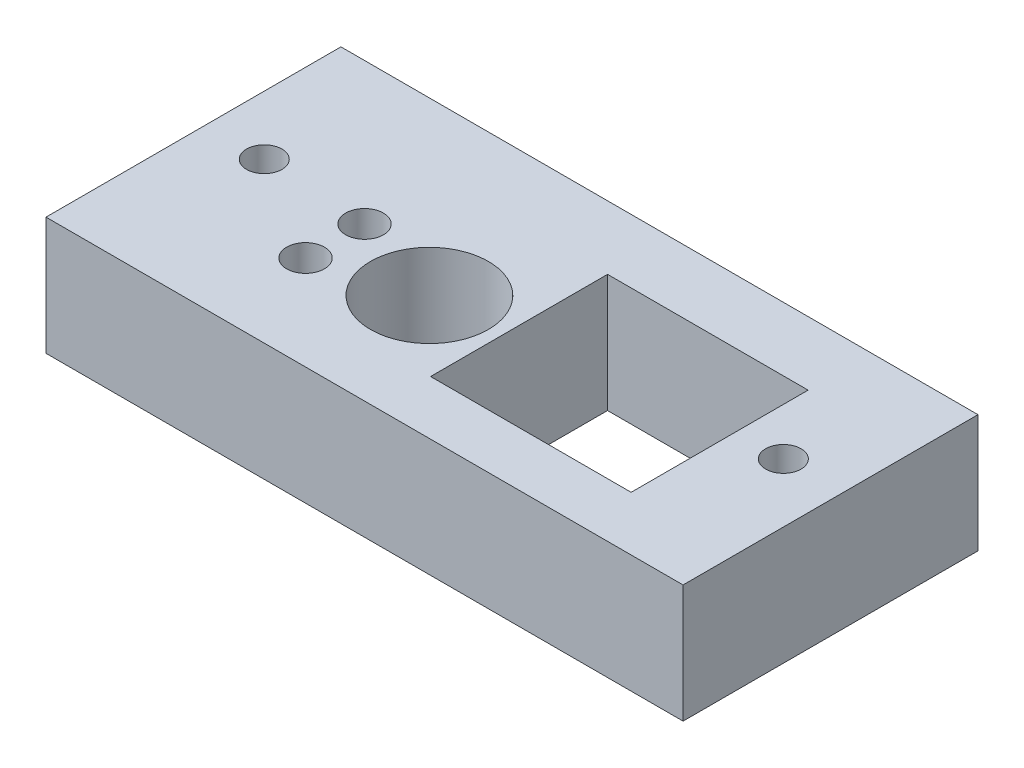
SolidWorks part; units mm, degrees
ref_plane "Front Plane" through (0, 0, 0) normal (0, 0, 1) x (1, 0, 0)
ref_plane "Top Plane" through (0, 0, 0) normal (0, 1, 0) x (1, 0, 0)
ref_plane "Right Plane" through (0, 0, 0) normal (1, 0, 0) x (0, 0, -1)
sketch "Sketch1" plane through (0, 0, 0) normal (0, 1, 0) x (1, 0, 0)
  line L1 (0, 0) -> (54, 0)
  line L2 (0, 0) -> (0, 25)
  line L3 (0, 25) -> (54, 25)
  line L4 (54, 0) -> (54, 25)
  dimension "D1" = 54
  dimension "D2" = 25
extrude "Boss-Extrude1" add sketch "Sketch1" along normal blind 10
sketch "Sketch2" plane through (0, 10, 0) normal (0, 1, 0) x (1, 0, 0)
  line L1 (28, 19.6) -> (45, 19.6)
  line L2 (28, 19.6) -> (28, 4.6)
  line L3 (28, 4.6) -> (45, 4.6)
  line L4 (45, 19.6) -> (45, 4.6)
  line L6 (5, 3.8) -> (49, 3.8) construction
  line L7 (5, 3.8) -> (5, 22.7304) construction
  circle A0 centre (49, 13.5) radius 1.5
  circle A1 centre (5, 13.5) radius 1.5
  circle A2 centre (22, 10.5) radius 5
  circle A3 centre (14, 13) radius 1.6
  circle A4 centre (14, 8) radius 1.6
  dimension "D11" = 3
  dimension "D12" = 3
  dimension "D13" = 10
  dimension "D8" = 3.2
  dimension "D19" = 3.2
  dimension "D2" = 15
  dimension "D3" = 0.8
  dimension "D4" = 6.7
  dimension "D5" = 17
  dimension "D6" = 4.2
  dimension "D7" = 9.2
  dimension "D9" = 9.7
  dimension "D10" = 9.7
  dimension "D14" = 9
  dimension "D15" = 44
  dimension "D16" = 9
  dimension "D17" = 17
  dimension "D18" = 40
extrude "Cut-Extrude1" cut sketch "Sketch2" against normal blind 10
